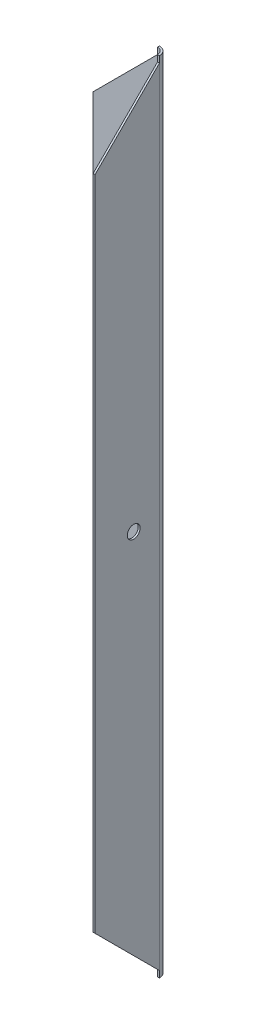
SolidWorks part; units mm, degrees
ref_plane "Front" through (0, 0, 0) normal (0, 0, 1) x (1, 0, 0)
ref_plane "Top" through (0, 0, 0) normal (0, 1, 0) x (1, 0, 0)
ref_plane "Right" through (0, 0, 0) normal (1, 0, 0) x (0, 0, -1)
sketch "Sketch1" plane through (0, 0, 0) normal (1, 0, 0) x (0, 0, -1)
  line L0 (0, -255) -> (0, 255)
  line L1 (0, 0) -> (55, 0) construction
  line L2 (55, 310) -> (55, -310)
  line L3 (55, 310) -> (0, 255)
  line L4 (0, -255) -> (55, -310)
  line L6 (55, 310) -> (56.5, 310)
  line L7 (55, 310) -> (55, -310)
  line L8 (55, -310) -> (56.5, -310)
  line L9 (56.5, 310) -> (56.5, -310)
  point P4 (0, 0)
  point P9 (55, 0)
  dimension "D1" = 620
  dimension "D2" = 55
  dimension "D3" = 45
  dimension "D4" = 1.5
extrude "Boss-Extrude1" add sketch "Sketch1" along normal blind 1.5 contours L0 L1 L2 L3 | L1 L0 L4 L7 | L9 L6 L2 L7 L8 region at (0, -141.6962, -28.3923) region at (0, 141.6962, -28.3923) region at (0, 0, -55.75)
sketch "Sketch2" plane through (0, 0, -56.5) normal (0, 0, -1) x (-1, 0, 0)
  line L0 (0, 0) -> (55, 0) construction
  line L1 (55, 255) -> (55, -255)
  line L2 (55, 255) -> (0, 310)
  line L3 (55, -255) -> (0, -310)
  line L4 (0, -310) -> (0, 310)
  point P6 (55, 0)
  dimension "D1" = 55
  dimension "D2" = 45
extrude "Boss-Extrude3" add sketch "Sketch2" against normal blind 1.5
sketch "Sketch5" plane through (0, -310, 0) normal (0, -1, 0) x (1, 0, 0)
  line L0 (0, 0) -> (0, -55) construction
  line L1 (0, -55) -> (-55, -55) construction
  line L2 (-5, -55) -> (-5, -56.5)
  line L3 (0, -50) -> (1.5, -50)
  line L4 (-5, -56.5) -> (1.5, -56.5)
  line L5 (1.5, -56.5) -> (1.5, -50)
  arc A0 (-5, -55) -> (0, -50) centre (-5, -50) ccw
  arc A1 (-5, -56.5) -> (1.5, -50) centre (-5, -50) ccw
  circle A2 centre (-5, -50) radius 6.5 construction
  circle A3 centre (-5, -50) radius 5 construction
  line M3 (0, -55) -> (0, -56.5)
  line M4 (0, -56.5) -> (1.5, -56.5)
  line M5 (1.5, -56.5) -> (1.5, -55)
  line M6 (1.5, -55) -> (0, -55)
  dimension "D1" = 10
  dimension "D2" = 1.5
extrude "Cut-Extrude1" cut sketch "Sketch5" against normal through all both and the other way through all contours A1 L4 L5 M3 M6 | M6 M3 M4 M5 region at (-0.1836, -310, -54.8164) region at (0.75, -310, -55.75)
extrude "Boss-Extrude4" add sketch "Sketch5<3>" against normal blind 620 contours L2 A1 L3 A0 region at (-1.3187, -310, -53.6813)
sketch "Sketch5<3>" plane through (0, -310, 0) normal (0, -1, 0) x (1, 0, 0) same geometry as "Sketch5"
sketch "Sketch6" plane through (1.5, 0, 0) normal (1, 0, 0) x (0, 0, -1)
  line L0 (50, 305) -> (50, -305) construction
  line L1 (56.5, 310) -> (50, 310) construction
  circle A0 centre (30, 0) radius 5
  dimension "D1" = 10
  dimension "D2" = 20
  dimension "D3" = 310
extrude "Cut-Extrude2" cut sketch "Sketch6" against normal through all both
sketch "Sketch7" plane through (0, 0, -56.5) normal (0, 0, -1) x (-1, 0, 0)
  line L0 (5, 305) -> (5, -305) construction
  circle A0 centre (25, 0) radius 5
  dimension "D1" = 10
  dimension "D2" = 20
  dimension "D3" = 310
extrude "Cut-Extrude3" cut sketch "Sketch7" against normal through all both
